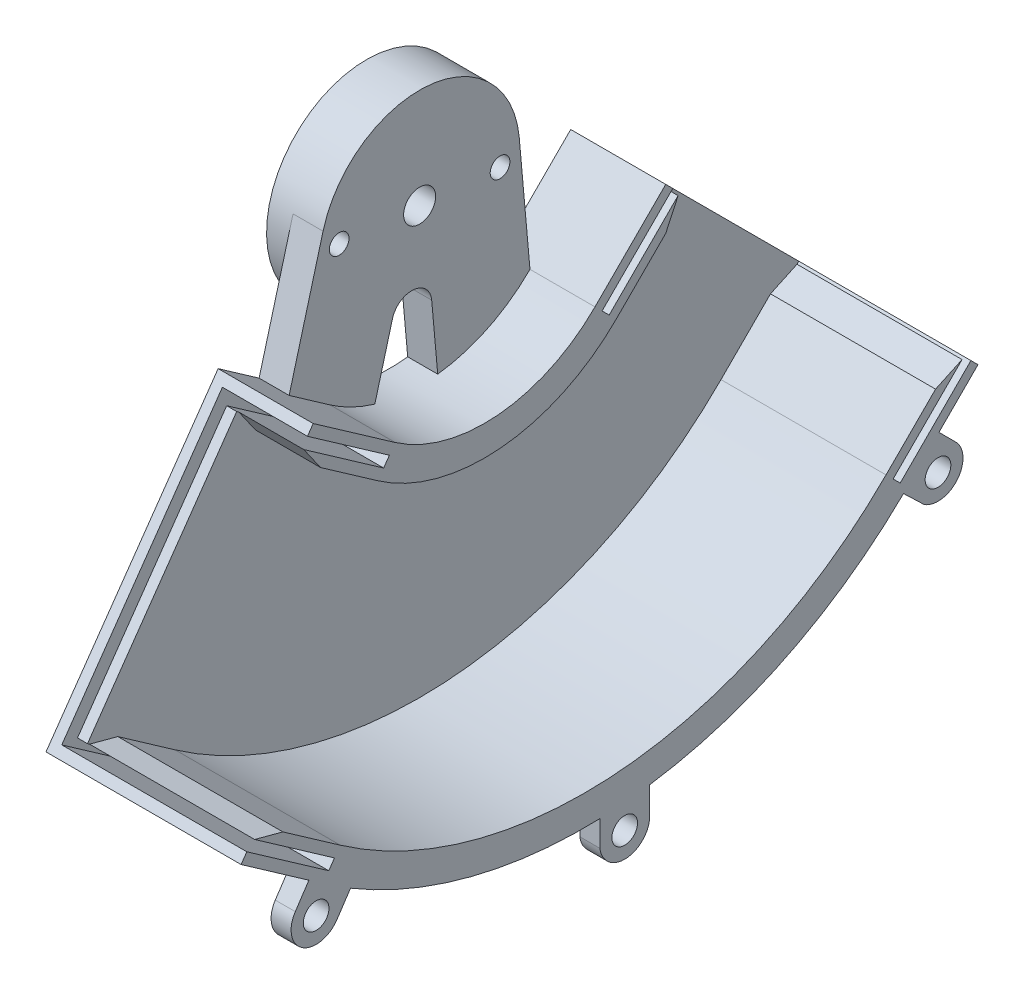
SolidWorks part; units mm, degrees
ref_plane "Front Plane" through (0, 0, 0) normal (0, 0, 1) x (1, 0, 0)
ref_plane "Top Plane" through (0, 0, 0) normal (0, 1, 0) x (1, 0, 0)
ref_plane "Right Plane" through (0, 0, 0) normal (1, 0, 0) x (0, 0, -1)
sketch "Sketch3" plane through (0, 0, 0) normal (1, 0, 0) x (0, 0, -1)
  line L0 (-22.7274, -32.4581) -> (-62.0633, -88.6355)
  line L1 (28.0184, -28.0184) -> (76.5118, -76.5118)
  line L2 (-22.7274, -32.4581) -> (0, 0) construction
  line L3 (0, 0) -> (28.0184, -28.0184) construction
  line L4 (0, 40.513) -> (0, -40.513) construction
  line L5 (-62.0633, -88.6355) -> (-66.4339, -94.8775)
  line L6 (76.5118, -76.5118) -> (81.8999, -81.8999)
  arc A2 (-62.0633, -88.6355) -> (76.5118, -76.5118) centre (0, 0) ccw
  arc A4 (-27.098, -38.7) -> (33.4066, -33.4066) centre (0, 0) ccw
  arc A5 (-22.7274, -32.4581) -> (28.0184, -28.0184) centre (0, 0) ccw
  arc A6 (-66.4339, -94.8775) -> (81.8999, -81.8999) centre (0, 0) ccw
  dimension "D1" = 216.408
  dimension "D2" = 135
  dimension "D3" = 94.488
  dimension "D4" = 7.62
  dimension "D6" = 7.62
  dimension "D5" = 80
extrude "Base extrude" add sketch "Sketch3" along normal blind 58.42 contours L5 A6 L6 A2 | A5 L0 A4 L1 region at (0, -39.9408, -3.4944) region at (0, -109.321, -9.5643)
sketch "Sketch4" plane through (58.42, 0, 0) normal (1, 0, 0) x (0, 0, -1)
  line L0 (-66.4339, -94.8775) -> (-22.7274, -32.4581)
  line L1 (28.0184, -28.0184) -> (81.8999, -81.8999)
  arc A0 (-22.7274, -32.4581) -> (28.0184, -28.0184) centre (0, 0) ccw
  arc A1 (-22.7274, -32.4581) -> (28.0184, -28.0184) centre (0, 0) ccw construction
  arc A2 (-66.4339, -94.8775) -> (81.8999, -81.8999) centre (0, 0) ccw
  arc A3 (-66.4339, -94.8775) -> (81.8999, -81.8999) centre (0, 0) ccw construction
  arc M1 (28.0184, -28.0184) -> (-22.7274, -32.4581) centre (0, 0) cw
  line M2 (-22.7274, -32.4581) -> (-27.098, -38.7)
  arc M3 (-27.098, -38.7) -> (33.4066, -33.4066) centre (0, 0) ccw
  line M4 (33.4066, -33.4066) -> (28.0184, -28.0184)
extrude "Outer wall" add sketch "Sketch4" along normal blind 7.62 contours L0 A2 L1 M3 | M4 M1 M2 M3 region at (58.42, -79.1939, -6.9286) region at (58.42, -39.9408, -3.4944)
ref_plane "Midplane" through (29.21, 0, 0) normal (-1, 0, 0) x (0, 0, 1)
mirror "Mirror1" about plane through (29.21, 0, 0) normal (-1, 0, 0) of "Outer wall"
sketch "Sketch6" plane through (0, 0, 0) normal (0, 0.5736, 0.8192) x (1, 0, 0)
  line L27 (-5.08, -42.164) -> (63.5, -42.164)
  line L28 (-5.08, -42.164) -> (-5.08, -113.284)
  line L29 (-5.08, -113.284) -> (63.5, -113.284)
  line L30 (63.5, -42.164) -> (63.5, -113.284)
  line L31 (-2.54, -44.704) -> (60.96, -44.704)
  line L32 (-2.54, -44.704) -> (-2.54, -110.744)
  line L33 (-2.54, -110.744) -> (60.96, -110.744)
  line L34 (60.96, -44.704) -> (60.96, -110.744)
  line L35 (58.42, -47.244) -> (0, -47.244) construction
  line L36 (0, -108.204) -> (0, -18.7894) construction
  line L37 (58.42, -18.7894) -> (58.42, -108.204) construction
  line L38 (58.42, -108.204) -> (0, -108.204) construction
  line L40 (0, -47.244) -> (58.42, -47.244)
  line L41 (0, -47.244) -> (0, -108.204)
  line L42 (0, -108.204) -> (58.42, -108.204)
  line L43 (58.42, -47.244) -> (58.42, -108.204)
  line L44 (-7.62, -39.624) -> (66.04, -39.624)
  line L45 (-7.62, -39.624) -> (-7.62, -115.824)
  line L46 (-7.62, -115.824) -> (66.04, -115.824)
  line L47 (66.04, -39.624) -> (66.04, -115.824)
  line M21 (-7.62, -39.624) -> (-7.62, -115.824)
  line M22 (-7.62, -115.824) -> (66.04, -115.824)
  line M23 (66.04, -115.824) -> (66.04, -39.624)
  line M24 (66.04, -39.624) -> (-7.62, -39.624)
  line M25 (58.42, -108.204) -> (0, -108.204)
  line M26 (0, -108.204) -> (0, -47.244)
  line M27 (0, -47.244) -> (58.42, -47.244)
  line M28 (58.42, -47.244) -> (58.42, -108.204)
  dimension "D1" = 2.54
  dimension "D2" = 2.54
  dimension "D3" = 2.54
  dimension "D4" = 2.54
  dimension "D5" = 2.54
  dimension "D6" = 2.54
  dimension "D7" = 2.54
  dimension "D8" = 2.54
extrude "Endcap 1" add sketch "Sketch6" along normal blind 25.4 contours L27 L30 L29 L28 M24 M21 M22 M23 | L34 L31 L32 L33 M28 M25 M26 M27 region at (29.21, -37.3698, 26.1667) region at (29.21, -33.3262, 23.3353)
sketch "Sketch7" plane through (0, 0, 0) normal (0, 0.7071, -0.7071) x (1, 0, 0)
  line L0 (-5.08, 113.284) -> (63.5, 113.284)
  line L1 (-5.08, 113.284) -> (-5.08, 42.164)
  line L2 (-5.08, 42.164) -> (63.5, 42.164)
  line L3 (63.5, 113.284) -> (63.5, 42.164)
  line L4 (-2.54, 110.744) -> (60.96, 110.744)
  line L5 (-2.54, 110.744) -> (-2.54, 44.704)
  line L6 (-2.54, 44.704) -> (60.96, 44.704)
  line L7 (60.96, 110.744) -> (60.96, 44.704)
  line L8 (0, 108.204) -> (58.42, 108.204)
  line L9 (0, 108.204) -> (0, 47.244)
  line L10 (0, 47.244) -> (58.42, 47.244)
  line L11 (58.42, 108.204) -> (58.42, 47.244)
  line L12 (-7.62, 115.824) -> (66.04, 115.824)
  line L13 (-7.62, 115.824) -> (-7.62, 39.624)
  line L14 (-7.62, 39.624) -> (66.04, 39.624)
  line L15 (66.04, 115.824) -> (66.04, 39.624)
  line L16 (58.42, 108.204) -> (0, 108.204) construction
  line L17 (58.42, 47.244) -> (58.42, 108.204) construction
  line L18 (66.04, 115.824) -> (-7.62, 115.824) construction
  line L19 (66.04, 39.624) -> (66.04, 115.824) construction
  line L20 (-7.62, 39.624) -> (-7.62, 115.824) construction
  line L21 (66.04, 39.624) -> (-7.62, 39.624) construction
  line M17 (66.04, 115.824) -> (-7.62, 115.824)
  line M18 (-7.62, 115.824) -> (-7.62, 39.624)
  line M19 (-7.62, 39.624) -> (66.04, 39.624)
  line M20 (66.04, 39.624) -> (66.04, 115.824)
  line M21 (0, 47.244) -> (0, 108.204)
  line M22 (0, 108.204) -> (58.42, 108.204)
  line M23 (58.42, 108.204) -> (58.42, 47.244)
  line M24 (58.42, 47.244) -> (0, 47.244)
  dimension "D1" = 2.54
  dimension "D2" = 2.54
  dimension "D3" = 2.54
  dimension "D4" = 2.54
  dimension "D5" = 2.54
  dimension "D6" = 2.54
  dimension "D7" = 2.54
  dimension "D8" = 2.54
extrude "Endcap 2" add sketch "Sketch7" along normal blind 25.4 contours L0 L3 L2 L1 M20 M17 M18 M19 | L7 L4 L5 L6 M24 M21 M22 M23 region at (29.21, -77.66, -77.66) region at (29.21, -81.1505, -81.1505)
chamfer "Internal Chamfer" distance 7.62 angle 20 4 edges at (29.21, -74.0667, 82.8697) (29.21, -24.1312, 47.9045) (29.21, -58.5513, -94.4723) (29.21, -15.446, -51.3671) first distance on face at (29.21, -81.3511, 72.4665) first distance on face at (29.21, -31.4156, 37.5013) first distance on face at (29.21, -67.5315, -85.492) first distance on face at (29.21, -24.4263, -42.3868)
ref_plane "Plane2" through (0, -13.9736, -1.2225) normal (0, -0.9962, -0.0872) x (-1, 0, 0)
sketch "Sketch10" plane through (0, -13.9736, -1.2225) normal (0, -0.9962, -0.0872) x (-1, 0, 0)
  line L0 (-66.04, 93.9078) -> (7.62, 93.9078) construction
  line L1 (-16.51, 95.5358) -> (-41.91, 95.5358)
  line L2 (-16.51, 95.5358) -> (-16.51, -82.1857)
  line L3 (-16.51, -82.1857) -> (-41.91, -82.1857)
  line L4 (-41.91, 95.5358) -> (-41.91, -82.1857)
  point P4 (-29.21, 93.9078)
  point P5 (-29.21, 95.5358)
  dimension "D1" = 25.4
extrude "Flywheel Hole" cut sketch "Sketch10" along normal up to next
sketch "Sketch11" plane through (-7.62, 0, 0) normal (-1, 0, 0) x (0, 0, 1)
  line L0 (-25.2982, 2.2719) -> (-28.0184, -28.0184)
  line L4 (-3.0636, -22.3183) -> (-4.5937, -39.3568)
  line L5 (6.8995, -21.445) -> (11.3704, -37.9575)
  line L6 (-20.4217, -1.79) -> (20.4217, 1.79) construction
  line L7 (24.5172, 6.6383) -> (33.1306, -25.1737)
  line L8 (43.5339, -17.8892) -> (22.7274, -32.4581) construction
  line L10 (1.5525, -17.7121) -> (-2.2178, 25.303) construction
  line L11 (22.7274, -32.4581) -> (43.5339, -17.8892)
  line L12 (22.7274, -32.4581) -> (33.1306, -25.1737)
  arc A1 (-28.0184, -28.0184) -> (22.7274, -32.4581) centre (0, 0) ccw construction
  circle A3 centre (0, 0) radius 4.064
  arc A4 (24.5172, 6.6383) -> (-25.2982, 2.2719) centre (0, 0) ccw
  circle A6 centre (-20.4217, -1.79) radius 2.5
  circle A7 centre (20.4217, 1.79) radius 2.5
  arc A8 (-3.0636, -22.3183) -> (6.8995, -21.445) centre (1.9961, -22.7727) cw
  arc A11 (11.3704, -37.9575) -> (22.7274, -32.4581) centre (0, 0) ccw
  arc A12 (-28.0184, -28.0184) -> (22.7274, -32.4581) centre (0, 0) ccw
  arc A13 (-28.0184, -28.0184) -> (-4.5937, -39.3568) centre (0, 0) ccw
  point P22 (0, 0)
  dimension "D3" = 8.128
  dimension "D2" = 25.4
  dimension "D1" = 5
  dimension "D5" = 5.08
  dimension "D4" = 41
  dimension "D7" = 43.18
  dimension "D6" = 0
extrude "Flywheel holder" add sketch "Sketch11" against normal blind 7.62
sketch "Sketch12" plane through (-7.62, 0, 0) normal (-1, 0, 0) x (0, 0, 1)
  circle A0 centre (0, 0) radius 14.605
  dimension "D1" = 29.21
extrude "Motor insert" cut sketch "Sketch12" against normal blind 6.35
sketch "Sketch13" plane through (66.04, 0, 0) normal (1, 0, 0) x (0, 0, -1)
  line L1 (-110.5367, 4.1813) -> (110.9716, 4.1813)
  line L2 (-110.5367, 4.1813) -> (-110.5367, -123.3274)
  line L3 (-110.5367, -123.3274) -> (110.9716, -123.3274)
  line L4 (110.9716, 4.1813) -> (110.9716, -123.3274)
extrude "Cut-Extrude1" cut sketch "Sketch13" against normal up to surface (24.13 mm away) up to face at (41.91, -26.9401, -2.3569)
sketch "Sketch14" plane through (41.91, 0, 0) normal (1, 0, 0) x (0, 0, -1)
  line L0 (-73.4762, -97.5482) -> (-70.0245, -92.3633)
  line L1 (-66.4339, -94.8775) -> (-87.2404, -80.3086) construction
  line L2 (-70.0245, -92.3633) -> (-59.4528, -99.401)
  line L3 (-59.4528, -99.401) -> (-62.9045, -104.586)
  line L4 (3.8593, -122.286) -> (3.8593, -115.7597)
  line L5 (3.8593, -115.7597) -> (16.51, -114.6413)
  line L6 (16.51, -114.6413) -> (16.51, -121.4959)
  line L7 (86.1731, -87.8533) -> (80.953, -82.836)
  line L8 (80.953, -82.836) -> (89.843, -73.7664)
  line L10 (89.843, -73.7664) -> (94.5478, -78.4712)
  line L11 (99.8604, -63.9394) -> (81.8999, -81.8999) construction
  circle A0 centre (-68.1904, -101.0671) radius 3.2639
  circle A1 centre (89.7004, -82.5731) radius 3.2639
  circle A2 centre (10.16, -121.4959) radius 3.2639
  arc A3 (-73.4762, -97.5482) -> (-62.9045, -104.586) centre (-68.1904, -101.0671) ccw
  arc A4 (3.8593, -122.286) -> (16.51, -121.4959) centre (10.16, -121.4959) ccw
  arc A5 (86.1731, -87.8533) -> (93.8023, -77.7257) centre (89.7004, -82.5731) ccw
  arc A6 (-66.4339, -94.8775) -> (81.8999, -81.8999) centre (0, 0) ccw construction
  line M9 (-87.2404, -80.3086) -> (-66.4339, -94.8775)
  arc M10 (-66.4339, -94.8775) -> (81.8999, -81.8999) centre (0, 0) ccw
  line M11 (81.8999, -81.8999) -> (99.8604, -63.9394)
  dimension "D7" = 6.5278
  dimension "D8" = 12.7
  dimension "D1" = 121.92
  dimension "D2" = 121.92
  dimension "D3" = 19.05
  dimension "D4" = 10.16
  dimension "D5" = 121.92
  dimension "D6" = 10.16
  dimension "D9" = 12.7
  dimension "D10" = 12.7
  dimension "D11" = 12.7
extrude "Joining connectors" add sketch "Sketch14" against normal blind 5.08 contours L7 A5 L10 A1 M11 M10 | L0 A3 L3 A0 M10 M9 | L5 L6 A4 L4 | A2 region at (41.91, -82.521, -81.5777) region at (41.91, -95.0739, 71.573)
sketch "Sketch15" plane through (-7.62, 0, 0) normal (-1, 0, 0) x (0, 0, 1)
  line L0 (-35.56, -110.2301) -> (-35.56, -132.08)
  line L1 (-35.56, -132.08) -> (30.48, -132.08)
  line L2 (30.48, -132.08) -> (30.48, -111.7415)
  circle A0 centre (20.32, -121.92) radius 3.2639
  circle A1 centre (-25.4, -121.92) radius 3.2639
  arc A2 (-81.8999, -81.8999) -> (66.4339, -94.8775) centre (0, 0) ccw construction
  circle A4 centre (-10.16, -121.4959) radius 3.2639
  arc A5 (-81.8999, -81.8999) -> (66.4339, -94.8775) centre (0, 0) ccw
  arc A6 (-81.8999, -81.8999) -> (66.4339, -94.8775) centre (0, 0) ccw
  circle A7 centre (-10.16, -121.4959) radius 3.2639 construction
  arc M16 (-81.8999, -81.8999) -> (66.4339, -94.8775) centre (0, 0) ccw
  dimension "D1" = 6.5278
  dimension "D2" = 25.4
  dimension "D3" = 20.32
  dimension "D5" = 10.16
  dimension "D6" = 10.16
  dimension "D7" = 10.16
  dimension "D8" = 121.92
  dimension "D4" = 0
extrude "80-20 connectors" add sketch "Sketch15" against normal blind 5.08 contours L1 L2 L0 A4 A1 A0 M16 region at (-7.62, -123.2019, -2.8038)
fillet "Fillet1" radius 30.48 2 edges at (-5.08, -111.7415, 30.48) (-5.08, -110.2301, -35.56)
fillet "Fillet2" radius 15.24 2 edges at (-5.08, -132.08, -35.56) (-5.08, -132.08, 30.48)
sketch "Sketch18" plane through (-1.27, 0, 0) normal (-1, 0, 0) x (0, 0, 1)
  circle A0 centre (0, 0) radius 4.064
  circle A1 centre (0, 0) radius 14.605
  circle A2 centre (0, 0) radius 14.605 construction
  circle A3 centre (0, 0) radius 4.064 construction
extrude "Boss-Extrude3" add sketch "Sketch18" along normal blind 5.842
sketch "Sketch20" plane through (-7.62, 0, 0) normal (-1, 0, 0) x (0, 0, 1)
  line L5 (6.8995, -21.445) -> (11.3704, -37.9575)
  line L6 (-4.5937, -39.3568) -> (-3.0636, -22.3183)
  line L7 (6.8995, -21.445) -> (7.6509, -24.2203)
  line L8 (-3.3207, -25.182) -> (-3.0636, -22.3183)
  circle A0 centre (0, 0) radius 14.605
  arc A1 (7.6509, -24.2203) -> (-3.3207, -25.182) centre (0, 0) ccw
  circle A2 centre (20.4217, 1.79) radius 2.5
  circle A3 centre (-20.4217, -1.79) radius 2.5
  circle A4 centre (-20.4217, -1.79) radius 2.5 construction
  circle A5 centre (20.4217, 1.79) radius 2.5 construction
  arc A6 (24.5172, 6.6383) -> (-25.2982, 2.2719) centre (0, 0) ccw construction
  circle A7 centre (0, 0) radius 14.605 construction
  arc A12 (6.8995, -21.445) -> (-3.0636, -22.3183) centre (1.9961, -22.7727) ccw
  arc A13 (6.8995, -21.445) -> (-3.0636, -22.3183) centre (1.9961, -22.7727) ccw
  dimension "D1" = 0
extrude "Boss-Extrude5" add sketch "Sketch20" along normal blind 5.842
